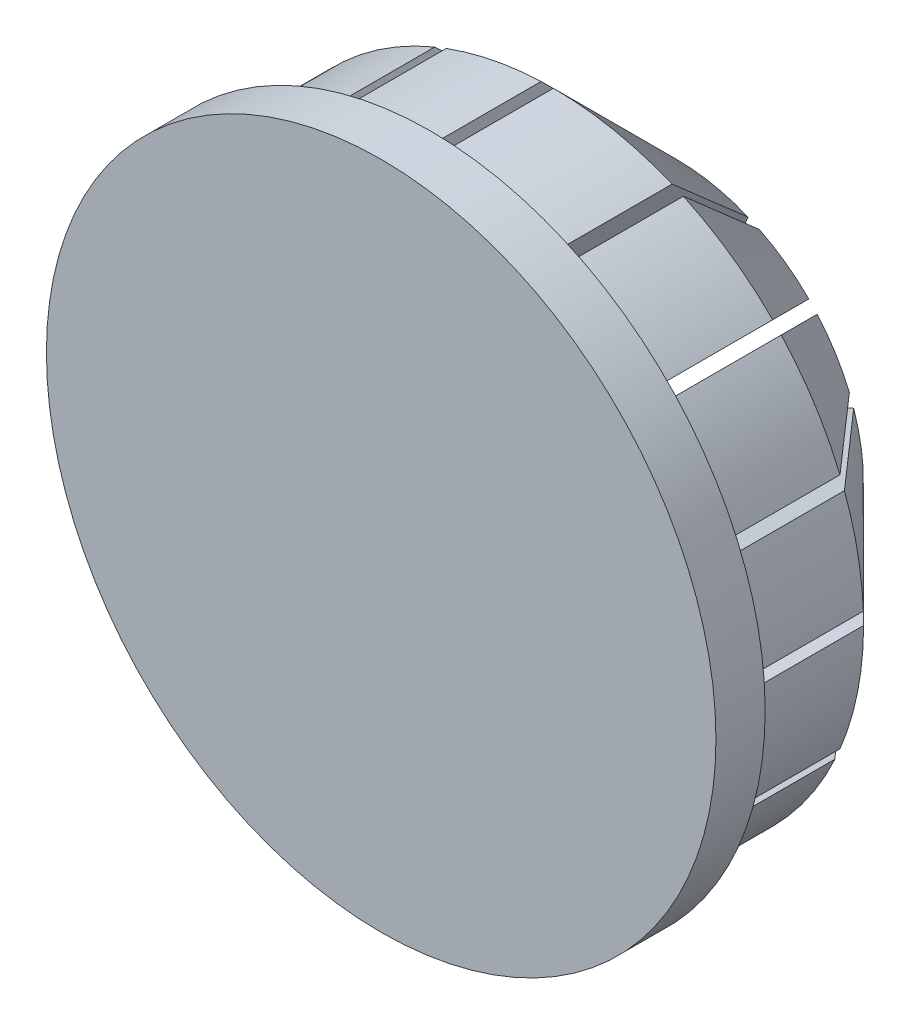
SolidWorks part; units mm, degrees
material "moto_Chrome Stainless Steel"
ref_plane "Front Plane" through (0, 0, 0) normal (0, 0, 1) x (1, 0, 0)
ref_plane "Top Plane" through (0, 0, 0) normal (0, 1, 0) x (1, 0, 0)
ref_plane "Right Plane" through (0, 0, 0) normal (1, 0, 0) x (0, 0, -1)
sketch "Sketch1" plane through (0, 0, 0) normal (0, 0, 1) x (1, 0, 0)
  line L0 (0, 37) -> (0, -37)
  line L1 (37, 0) -> (-37, 0)
  line L2 (0, 0) -> (26.163, 26.163)
  line L3 (0, 0) -> (-26.163, 26.163)
  line L4 (0, 0) -> (-26.163, -26.163)
  line L5 (0, 0) -> (26.163, -26.163)
  line L6 (0, 0) -> (34.1835, 14.1593)
  line L7 (0, 0) -> (-34.1835, 14.1593)
  line L8 (0, 0) -> (34.1835, -14.1593)
  line L9 (0, 0) -> (-34.1835, -14.1593)
  line L10 (0, 0) -> (14.1593, 34.1835)
  line L11 (0, 0) -> (-14.1593, 34.1835)
  line L12 (0, 0) -> (-14.1593, -34.1835)
  line L13 (0, 0) -> (14.1593, -34.1835)
  line L14 (0.4619, -0.1913) -> (14.6212, 33.9922)
  line L15 (0.4619, 0.1913) -> (-13.6973, 34.3749)
  line L16 (0.3536, 0.3536) -> (-25.8094, 26.5165)
  line L17 (0.1913, 0.4619) -> (-33.9922, 14.6212)
  line L18 (37, 0.5) -> (-37, 0.5)
  line L19 (-0.1913, 0.4619) -> (-34.3749, -13.6973)
  line L20 (-0.3536, 0.3536) -> (-26.5165, -25.8094)
  line L21 (-0.5, 37) -> (-0.5, -37)
  line L22 (-0.4619, 0.1913) -> (-14.6212, -33.9922)
  line L23 (-0.4619, -0.1913) -> (13.6973, -34.3749)
  line L24 (-0.3536, -0.3536) -> (25.8094, -26.5165)
  line L25 (-0.1913, -0.4619) -> (33.9922, -14.6212)
  line L26 (0.1913, -0.4619) -> (34.3749, 13.6973)
  line L27 (0.3536, -0.3536) -> (26.5165, 25.8094)
  circle A0 centre (0, 0) radius 40
  circle A1 centre (0, 0) radius 29.037
  circle A2 centre (0, 0) radius 26.037
  circle A3 centre (0, 0) radius 13.6054
  circle A4 centre (0, 0) radius 12.6054
  circle A5 centre (0, 0) radius 37
  circle A6 centre (0, 0) radius 3.7813
  dimension "D1" = 22.5
  dimension "D5" = 22.5
  dimension "D2" = 3
  dimension "D3" = 1
  dimension "D4" = 3
  dimension "D6" = 0.5
extrude "Boss-Extrude10" add sketch "Sketch1" along normal blind 2 contours A0 A5 region at (-38.8686, 0, 0)
sketch "Sketch4" plane through (0, 0, 2) normal (0, 0, 1) x (1, 0, 0)
  circle A2 centre (0, 0) radius 37
  circle A3 centre (0, 0) radius 37
  dimension "D1" = 0
extrude "Boss-Extrude12" add sketch "Sketch4" against normal blind 2
extrude "Boss-Extrude14" add sketch "Sketch1<20>" against normal blind 20 contours L21 A5 L15 A1 | L11 A5 L16 A1 | L3 A5 L17 A1 | L7 A5 L18 A1 | L1 A5 L19 A1 | L9 A5 L20 A1 | L4 A5 L22 A1 | L12 A5 L21 A1 | L0 A5 L23 A1 | L13 A5 L24 A1 | L5 A5 L25 A1 | L8 A5 L1 A1 | L18 A5 L26 A1 | L6 A5 L27 A1 | L2 A5 L14 A1 | L10 A5 L0 A1 region at (6.4313, 32.3323, 0) region at (-6.44, 32.3761, 0) region at (18.5333, 27.2898, 0) region at (-18.12, 27.5659, 0) region at (27.5659, 18.12, 0) region at (-27.2898, 18.5333, 0) region at (32.3761, 6.44, 0) region at (-32.3048, 6.6792, 0) region at (32.3323, -6.4313, 0) region at (-32.4018, -6.1917, 0) region at (27.2898, -18.5333, 0) region at (-27.5659, -18.12, 0) region at (18.12, -27.5659, 0) region at (-18.5333, -27.2898, 0) region at (6.1917, -32.4018, 0) region at (-6.6792, -32.3048, 0)
sketch "Sketch1<20>" plane through (0, 0, 0) normal (0, 0, 1) x (1, 0, 0) same geometry as "Sketch1"
extrude "Boss-Extrude15" add sketch "Sketch1<21>" against normal blind 15 contours A3 L5 A2 L25 | A3 L13 A2 L24 | A3 L0 A2 L23 | A3 L12 A2 L21 | A3 L4 A2 L22 | A3 L9 A2 L20 | A3 L1 A2 L19 | A3 L7 A2 L18 | A3 L3 A2 L17 | A3 L11 A2 L16 | A3 L21 A2 L15 | A3 L10 A2 L0 | A3 L2 A2 L14 | A3 L6 A2 L27 | A3 L18 A2 L26 | A3 L8 A2 L1 region at (3.9681, 19.9488, 0) region at (-3.9926, 20.0721, 0) region at (11.5393, 16.8223, 0) region at (-11.1259, 17.0986, 0) region at (17.0986, 11.1259, 0) region at (-16.8223, 11.5393, 0) region at (20.0721, 3.9926, 0) region at (-19.9577, 4.2233, 0) region at (19.9488, -3.9681, 0) region at (-20.0547, -3.7357, 0) region at (16.8223, -11.5393, 0) region at (-17.0986, -11.1259, 0) region at (11.1259, -17.0986, 0) region at (-11.5393, -16.8223, 0) region at (3.7357, -20.0547, 0) region at (-4.2233, -19.9577, 0)
sketch "Sketch1<21>" plane through (0, 0, 0) normal (0, 0, 1) x (1, 0, 0) same geometry as "Sketch1"
extrude "Boss-Extrude16" add sketch "Sketch1<22>" against normal blind 10 contours A6 L5 A4 L25 | A6 L13 A4 L24 | A6 L0 A4 L23 | A6 L12 A4 L21 | A6 L4 A4 L22 | A6 L9 A4 L20 | A6 L1 A4 L19 | A6 L7 A4 L18 | A6 L3 A4 L17 | A6 L11 A4 L16 | A6 L21 A4 L15 | A6 L10 A4 L0 | A6 L2 A4 L14 | A6 L6 A4 L27 | A6 L18 A4 L26 | A6 L8 A4 L1 region at (1.7417, 8.7561, 0) region at (-1.8166, 9.1325, 0) region at (5.2539, 7.4149, 0) region at (-4.8399, 7.6916, 0) region at (7.6916, 4.8399, 0) region at (-7.4149, 5.2539, 0) region at (9.1325, 1.8166, 0) region at (-8.8611, 2.0164, 0) region at (8.7561, -1.7417, 0) region at (-8.9582, -1.5281, 0) region at (1.5281, -8.9582, 0) region at (4.8399, -7.6916, 0) region at (7.4149, -5.2539, 0) region at (-2.0164, -8.8611, 0) region at (-7.6916, -4.8399, 0) region at (-5.2539, -7.4149, 0)
sketch "Sketch1<22>" plane through (0, 0, 0) normal (0, 0, 1) x (1, 0, 0) same geometry as "Sketch1"
chamfer "Chamfer6" distance 5 angle 45 16 edges at (-36.2395, 7.4634, -20) (-36.337, -6.973, -20) (-30.9026, -20.3478, -20) (-20.7635, -30.6248, -20) (-7.4634, -36.2395, -20) (6.973, -36.337, -20) (20.3478, -30.9026, -20) (30.6248, -20.7635, -20) (36.2891, -7.2183, -20) (36.2891, 7.2183, -20) (30.9026, 20.3478, -20) (20.7635, 30.6248, -20) (7.2183, 36.2891, -20) (-7.2183, 36.2891, -20) (-20.3478, 30.9026, -20) (-30.6248, 20.7635, -20)
chamfer "Chamfer7" distance 5 angle 45 32 edges at (-5.0796, 25.5367, -15) (-14.2568, 21.7869, -15) (-21.5091, 14.6726, -15) (-25.4867, 5.3245, -15) (-25.5843, -4.8341, -15) (-21.7869, -14.2568, -15) (14.6726, 21.5091, -15) (21.7869, 14.2568, -15) (25.5367, 5.0796, -15) (25.5367, -5.0796, -15) (21.5091, -14.6726, -15) (14.2568, -21.7869, -15) (4.8341, -25.5843, -15) (-5.3245, -25.4867, -15) (-14.6726, -21.5091, -15) (-7.7654, -11.1716, -15) (-11.4495, -7.3496, -15) (-13.3905, -2.4086, -15) (-13.2929, 2.8991, -15) (-11.1716, 7.7654, -15) (-7.3496, 11.4495, -15) (-2.6543, 13.3439, -15) (-2.8991, -13.2929, -15) (2.4086, -13.3905, -15) (7.3496, -11.4495, -15) (11.1716, -7.7654, -15) (13.3439, -2.6543, -15) (13.3439, 2.6543, -15) (11.4495, 7.3496, -15) (7.7654, 11.1716, -15) (2.6543, 13.3439, -15) (5.0796, 25.5367, -15)
chamfer "Chamfer8" distance 5 angle 45 16 edges at (7.2097, 10.34, -10) (10.6178, 6.7939, -10) (12.3632, 2.4592, -10) (12.3632, -2.4592, -10) (10.34, -7.2097, -10) (6.7939, -10.6178, -10) (2.2135, -12.4095, -10) (-2.7039, -12.3119, -10) (-7.2097, -10.34, -10) (-10.6178, -6.7939, -10) (-12.4095, -2.2135, -10) (-12.3119, 2.7039, -10) (-10.34, 7.2097, -10) (-6.7939, 10.6178, -10) (-2.4592, 12.3632, -10) (2.4592, 12.3632, -10)
chamfer "Chamfer9" distance 1 angle 45 16 edges at (-16.3394, -24.0036, -20) (-24.2814, -15.9236, -20) (-28.5268, -5.4194, -20) (-28.4292, 5.9098, -20) (-24.0036, 16.3394, -20) (-15.9236, 24.2814, -20) (5.6648, 28.479, -20) (-5.6648, 28.479, -20) (16.3394, 24.0036, -20) (24.2814, 15.9236, -20) (28.479, 5.6648, -20) (28.479, -5.6648, -20) (24.0036, -16.3394, -20) (15.9236, -24.2814, -20) (5.4194, -28.5268, -20) (-5.9098, -28.4292, -20)
sketch "Sketch5" plane through (0, 0, 2) normal (0, 0, 1) x (1, 0, 0)
  circle A0 centre (0, 0) radius 13.6054
  circle A1 centre (0, 0) radius 42.6054
  dimension "D1" = 29
extrude "Cut-Extrude1" cut sketch "Sketch5" against normal blind 31
